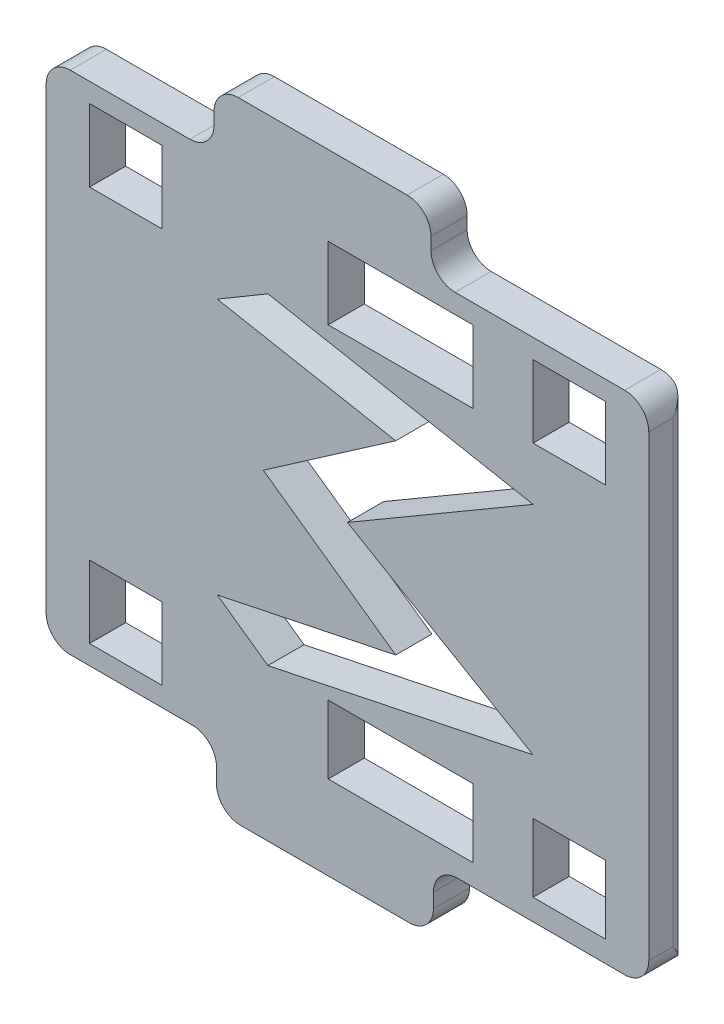
SolidWorks part; units mm, degrees
ref_plane "前视基准面" through (0, 0, 0) normal (0, 0, 1) x (1, 0, 0)
ref_plane "上视基准面" through (0, 0, 0) normal (0, 1, 0) x (1, 0, 0)
ref_plane "右视基准面" through (0, 0, 0) normal (1, 0, 0) x (0, 0, -1)
sketch "草图1" plane through (0, 0, 0) normal (0, 0, 1) x (1, 0, 0)
  line L0 (-55.35, 115) -> (-55.35, 120)
  line L1 (-115, 105) -> (-65.35, 105)
  line L2 (-125, 95) -> (-125, -95)
  line L3 (-115, -105) -> (-64.3399, -105)
  line L4 (125, 95) -> (125, -95)
  line L5 (-125, 105) -> (-121.8114, 102.3216) construction
  line L6 (-125, -105) -> (-121.8114, -102.3216) construction
  line L7 (-45.35, 130) -> (24.7747, 130)
  line L8 (34.65, 120.1247) -> (34.65, 115)
  line L9 (-54.3399, -115) -> (-54.3399, -121.0101)
  line L10 (-44.3399, -131.0101) -> (25.6601, -131.0101)
  line L11 (35.6601, -121.0101) -> (35.6601, -115)
  line L12 (44.65, 105) -> (115, 105)
  line L13 (45.6601, -105) -> (115, -105)
  line L14 (121.8114, -102.3216) -> (125, -105) construction
  line L15 (121.8114, 102.3216) -> (125, 105) construction
  arc A0 (-125, 95) -> (-115, 105) centre (-115, 95) cw
  arc A1 (-115, -105) -> (-125, -95) centre (-115, -95) cw
  arc A2 (125, 95) -> (115, 105) centre (115, 95) ccw
  arc A3 (115, -105) -> (125, -95) centre (115, -95) ccw
  arc A4 (-65.35, 105) -> (-55.35, 115) centre (-65.35, 115) ccw
  arc A5 (44.65, 105) -> (34.65, 115) centre (44.65, 115) cw
  arc A6 (-45.35, 130) -> (-55.35, 120) centre (-45.35, 120) ccw
  arc A7 (34.65, 120.1247) -> (24.7747, 130) centre (24.7747, 120.1247) ccw
  arc A8 (-54.3399, -115) -> (-64.3399, -105) centre (-64.3399, -115) ccw
  arc A9 (35.6601, -115) -> (45.6601, -105) centre (45.6601, -115) cw
  arc A10 (-44.3399, -131.0101) -> (-54.3399, -121.0101) centre (-44.3399, -121.0101) cw
  arc A11 (25.6601, -131.0101) -> (35.6601, -121.0101) centre (25.6601, -121.0101) ccw
  point P0 (0, 0)
  point P28 (-45.35, 105)
  point P32 (34.65, 105)
  point P40 (35.6601, -105)
  dimension "D1" = 10
  dimension "D2" = 10
  dimension "D3" = 10
  dimension "D4" = 10
  dimension "D5" = 10
  dimension "D6" = 10
  dimension "D9" = 10
  dimension "D11" = 9.8753
  dimension "D7" = 10
  dimension "D8" = 10
  dimension "D10" = 10
  dimension "D12" = 10
  dimension "D13" = 210
  dimension "D14" = 250
extrude "凸台-拉伸1" add sketch "草图1" along normal blind 15
sketch "草图2" plane through (0, 0, 15) normal (0, 0, 1) x (1, 0, 0)
  line L0 (125, -95) -> (125, 95) construction
  line L1 (-107, 97) -> (-77, 97)
  line L2 (-107, 97) -> (-107, 67)
  line L3 (-107, 67) -> (-77, 67)
  line L4 (-77, 97) -> (-77, 67)
  line L5 (-107, 97) -> (-77, 67) construction
  line L6 (-107, 67) -> (-77, 97) construction
  line L7 (-107, -67) -> (-77, -67)
  line L8 (-107, -67) -> (-107, -97)
  line L9 (-107, -97) -> (-77, -97)
  line L10 (-77, -67) -> (-77, -97)
  line L11 (-107, -67) -> (-77, -97) construction
  line L12 (-107, -97) -> (-77, -67) construction
  line L13 (77, 97) -> (107, 97)
  line L14 (77, 97) -> (77, 67)
  line L15 (77, 67) -> (107, 67)
  line L16 (107, 97) -> (107, 67)
  line L17 (77, 97) -> (107, 67) construction
  line L18 (77, 67) -> (107, 97) construction
  line L19 (77, -67.8217) -> (107, -67.8217)
  line L20 (77, -67.8217) -> (77, -96.1783)
  line L21 (77, -96.1783) -> (107, -96.1783)
  line L22 (107, -67.8217) -> (107, -96.1783)
  line L23 (77, -67.8217) -> (107, -96.1783) construction
  line L24 (77, -96.1783) -> (107, -67.8217) construction
  line L25 (-8, 97) -> (52, 97)
  line L26 (-8, 97) -> (-8, 67)
  line L27 (-8, 67) -> (52, 67)
  line L28 (52, 97) -> (52, 67)
  line L29 (-8, 97) -> (52, 67) construction
  line L30 (-8, 67) -> (52, 97) construction
  line L31 (-8, -67.8217) -> (52, -67.8217)
  line L32 (-8, -67.8217) -> (-8, -96.1783)
  line L33 (-8, -96.1783) -> (52, -96.1783)
  line L34 (52, -67.8217) -> (52, -96.1783)
  line L35 (-8, -67.8217) -> (52, -96.1783) construction
  line L36 (-8, -96.1783) -> (52, -67.8217) construction
  line L37 (-65.35, 105) -> (-115, 105) construction
  line L38 (-115, -105) -> (-64.3399, -105) construction
  line L39 (-125, 95) -> (-125, -95) construction
  point P0 (-92, 82)
  point P5 (-92, -82)
  point P10 (92, 82)
  point P15 (92, -82)
  point P20 (22, 82)
  point P25 (22, -82)
  dimension "D1" = 8
  dimension "D2" = 8
  dimension "D3" = 18
  dimension "D4" = 18
  dimension "D5" = 30
  dimension "D6" = 30
  dimension "D7" = 18
  dimension "D8" = 18
  dimension "D9" = 25
  dimension "D10" = 30
  dimension "D11" = 60
  dimension "D12" = 60
  dimension "D13" = 25
  dimension "D14" = 30
extrude "切除-拉伸1" cut sketch "草图2" against normal through all
sketch "草图3" plane through (0, 0, 15) normal (0, 0, 1) x (1, 0, 0)
  line L0 (-33, -67.9227) -> (77, -45)
  line L1 (77, -45) -> (0, 0)
  line L2 (0, 0) -> (77, 45)
  line L3 (77, 45) -> (-33, 65.6394)
  line L4 (77, -67.8217) -> (77, -96.1783) construction
  line L5 (77, 97) -> (77, 67) construction
  line L6 (-8, 97) -> (-8, 67) construction
  line L7 (-8, -67.8217) -> (-8, -96.1783) construction
  line L8 (-33, -67.9227) -> (-54, -53.043)
  line L9 (-54, -53.043) -> (20.0261, -37.6168)
  line L10 (20.0261, -37.6168) -> (-34.9076, 1.307)
  line L11 (-34.9076, 1.307) -> (20.0261, 39.3408)
  line L12 (20.0261, 39.3408) -> (-54, 53.2304)
  line L13 (-54, 53.2304) -> (-33, 65.6394)
  line L15 (52, -67.8217) -> (-8, -67.8217) construction
  dimension "D1" = 45
  dimension "D2" = 45
  dimension "D3" = 25
  dimension "D4" = 25
  dimension "D5" = 46
  dimension "D6" = 46
  dimension "D8" = 30.2049
extrude "切除-拉伸2" cut sketch "草图3" against normal through all
fillet "圆角2" radius 5 1 edges at (125, 0, 0) tangent propagation no
equation "\"45、\"=43.7672"
